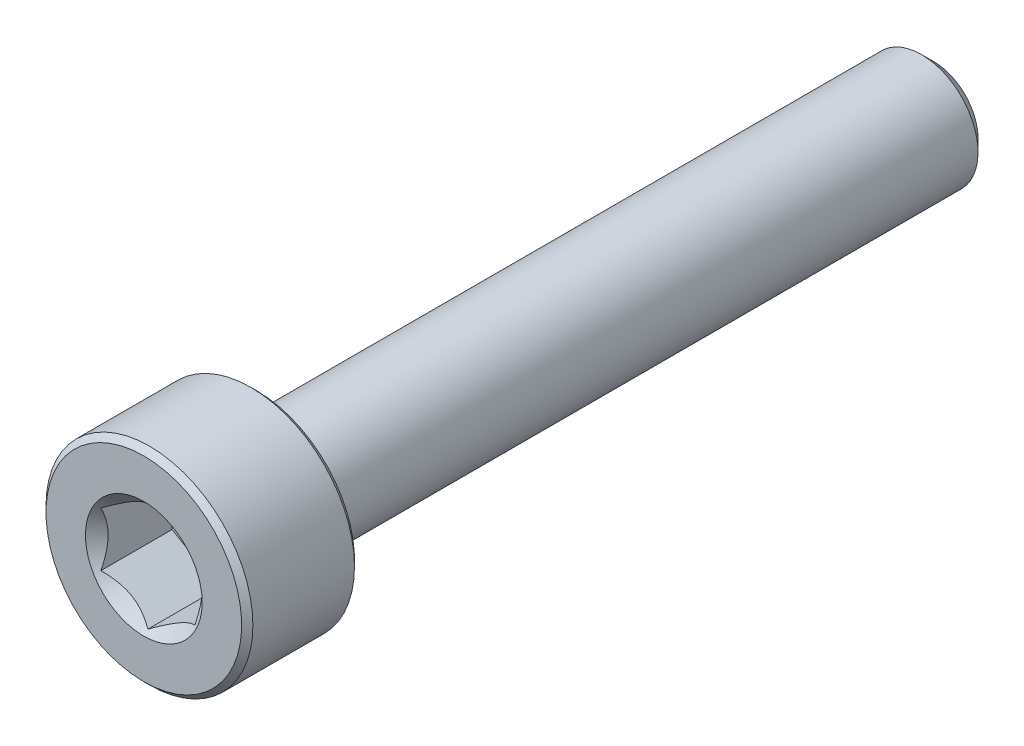
SolidWorks part; units mm, degrees
ref_plane "Front Plane" through (0, 0, 0) normal (0, 0, 1) x (1, 0, 0)
ref_plane "Top Plane" through (0, 0, 0) normal (0, 1, 0) x (1, 0, 0)
ref_plane "Right Plane" through (0, 0, 0) normal (1, 0, 0) x (0, 0, -1)
sketch "Sketch1" plane through (0, 0, 0) normal (1, 0, 0) x (0, 0, -1)
  line L0 (-10.5, 0) -> (10.5, 0) construction
  line L1 (10.5, 0) -> (10.5, 1.1752) construction
  line L2 (10.5, 1.1752) -> (10.1752, 1.5) construction
  line L3 (10.1752, 1.5) -> (10.125, 1.5) construction
  line L4 (10.125, 1.5) -> (-7.5, 1.5) construction
  line L5 (-7.5, 1.5) -> (-7.5, 2.75) construction
  line L6 (-7.5, 2.75) -> (-10.5, 2.75) construction
  line L7 (-10.5, 2.75) -> (-10.5, 0) construction
  line L8 (10.5, 1.1752) -> (10.5, 1.5) construction
  line L9 (10.4688, 1.5541) -> (10.7188, 1.1211) construction
  line L10 (10.7188, 1.1211) -> (10.9688, 1.5541) construction
  line L11 (10.9688, 1.5541) -> (10.4688, 1.5541) construction
  line L12 (10.7188, 1.5541) -> (10.7188, 1.5) construction
  line L13 (10.7188, 1.1211) -> (10.7188, 1.1752) construction
  line L14 (10.6875, 1.1752) -> (10.75, 1.1752) construction
  line L15 (10.5, 1.5) -> (10.9375, 1.5) construction
  line L16 (10.4844, 1.5271) -> (10.9531, 1.5271) construction
  line L17 (10.5, 0) -> (10.5, -1.5) construction
  line L18 (-7.65, 2.75) -> (-7.5, 2.6) construction
  line L19 (-10.35, 2.75) -> (-10.5, 2.6) construction
  line L20 (-7.5, 1.5) -> (-7.5, 0) construction
  line L21 (-7.5, 0.75) -> (-1.5, 0.75) construction
  line L22 (-1.5, 0.75) -> (4.5, 0.75) construction
  line L23 (4.5, 0.75) -> (10.5, 0.75) construction
  line L24 (-1.5, 0.75) -> (-1.5, 1.5) construction
  line L25 (-1.5, 1.5) -> (-1.5, 2.75) construction
  line L26 (4.5, 0.75) -> (4.5, 2.75) construction
  point P0 (-10.5, 1.25)
  point P3 (9.25, 1.5)
  point P4 (0, 0)
  point P18 (4.5, 1.5)
  point P22 (10.7188, 1.1752)
  point P24 (10.125, 1.5)
  point P25 (10.7188, 1.5)
  point P28 (10.7188, 1.5271)
  point P29 (9.25, -1.5)
  point P30 (-1.5, 1.5)
  point P31 (-9, 2.75)
  point P37 (-8.025, 2.75)
  point P38 (-10.275, 2.75)
  point P45 (-1.5, 0.75)
  point P46 (4.5, 0.75)
  dimension "D2" = 0.0625
  dimension "D7" = 0.15
  dimension "D8" = 0.15
  dimension "D9" = 0.15
  dimension "D10" = 0.075
  dimension "D11" = 0.375
  dimension "Drive Size" = 2.5
  dimension "Head Diameter" = 5.5
  dimension "Head Height" = 3
  dimension "Thread Pitch" = 0.5
  dimension "Thread Dia" = 3
  dimension "Length" = 18
  dimension "D12" = 0.375
  dimension "D4" = 1.25
  dimension "D3" = 45
sketch "Sketch2" plane through (0, 0, 0) normal (1, 0, 0) x (0, 0, -1)
  line L0 (-10.5, 0) -> (-10.5, 2.6)
  line L1 (-10.35, 2.75) -> (-7.65, 2.75)
  line L2 (-7.5, 2.6) -> (-7.5, 1.65)
  line L4 (10.1752, 1.5) -> (10.5, 1.1752)
  line L5 (10.5, 1.1752) -> (10.5, 0)
  line L6 (-7.5, 2.75) -> (-10.5, 2.75) construction
  line L7 (10.5, 0) -> (-10.5, 0)
  line L8 (-10.35, 2.75) -> (-10.5, 2.6) construction
  line L10 (-10.35, 2.75) -> (-10.5, 2.6)
  line L14 (-7.65, 2.75) -> (-7.5, 2.6) construction
  line L16 (-7.65, 2.75) -> (-7.5, 2.6)
  line L17 (-7.5, 1.5) -> (-7.5, 2.75) construction
  line L19 (-7.35, 1.5) -> (10.1752, 1.5)
  line L20 (10.125, 1.5) -> (-7.5, 1.5) construction
  arc A1 (-7.5, 1.65) -> (-7.35, 1.5) centre (-7.35, 1.65) ccw
  dimension "D3" = 0.15
revolve "Revolve1" add sketch "Sketch2" angle 360 about L7
sketch "Sketch3" plane through (0, 0, 10.5) normal (0, 0, 1) x (1, 0, 0)
  line L1 (1.25, -0.7217) -> (1.25, 0.7217)
  line L2 (1.25, 0.7217) -> (0, 1.4434)
  line L3 (0, 1.4434) -> (-1.25, 0.7217)
  line L4 (-1.25, 0.7217) -> (-1.25, -0.7217)
  line L5 (-1.25, -0.7217) -> (0, -1.4434)
  line L6 (0, -1.4434) -> (1.25, -0.7217)
  circle A0 centre (0, 0) radius 1.25 construction
  circle A1 centre (0, 0) radius 2.75 construction
  circle A2 centre (0, 0) radius 2.75 construction
  circle A3 centre (0, 0) radius 1.4434 construction
  point P13 (0, 0)
  dimension "D1" = 2.8868
extrude "Cut-Extrude1" cut sketch "Sketch3" against normal offset from surface (2 mm away) 1 up to face at (0, 2.6, 7.5)
sketch "Sketch4" plane through (0, 0, 10.5) normal (0, 0, 1) x (1, 0, 0)
  circle A0 centre (0, 0) radius 1.5516
  dimension "D1" = 3.1033
extrude "Cut-Extrude2" cut sketch "Sketch4" against normal up to vertex (1.5 mm away) draft 45 up to point (0, 2.75, 9)
sketch "Sketch11" plane through (0, 0, 0) normal (1, 0, 0) x (0, 0, -1)
  line L0 (-10.5, 0) -> (10.5, 0) construction
  line L1 (-10.5, 0) -> (10.5, 0) construction
  line L2 (-4.125, 0) -> (-4.125, 1.5) construction
  line L3 (10.125, 1.5) -> (-7.5, 1.5) construction
  line L4 (7.125, 0) -> (7.125, 1.5) construction
  line L6 (10.5, 1.1752) -> (10.5, 1.5) construction
  point P2 (-4.125, 0)
  point P3 (7.125, 0)
  dimension "D1" = 3.375
  dimension "D2" = 3.375
sketch "Sketch6" [suppressed] plane through (0, 0, -10.5) normal (0, 0, -1) x (-1, 0, 0)
  circle A0 centre (0, 0) radius 1.5
curve "Helix/Spiral1" [suppressed] pitch 0.5 height 18.5 turns 37
sketch "Sketch10" [suppressed] plane through (0, 0, 0) normal (1, 0, 0) x (0, 0, -1)
  line L0 (-7.35, -2.75) -> (-7.35, 2.75)
  line L5 (-10.5, 0) -> (10.5, 0) construction
  line L6 (-7.35, 1.5) -> (-7.35, -1.5) construction
  point P3 (-7.35, 0)
split "Split1" [suppressed] bodies to split 106
sketch "Sketch7" [suppressed] plane through (0, 0, 0) normal (1, 0, 0) x (0, 0, -1)
  line L0 (10.4844, 1.5271) -> (10.9531, 1.5271)
  line L1 (10.9531, 1.5271) -> (10.75, 1.1752)
  line L2 (10.75, 1.1752) -> (10.6875, 1.1752)
  line L3 (10.6875, 1.1752) -> (10.4844, 1.5271)
sweep "Cut-Sweep1" [suppressed] cut profiles "Sketch7" path "Helix/Spiral1"
sketch "Sketch8" [suppressed] plane through (0, 0, 0) normal (1, 0, 0) x (0, 0, -1)
  line L0 (-7.5, 0) -> (-7.5, 1.5)
  line L1 (-7.35, -1.5) -> (-7.35, 1.5) construction
  line L2 (-7.5, 1.5) -> (-7.35, 1.5)
  line L4 (-7.35, 1.5) -> (-6.484, 0)
  line L5 (-6.484, 0) -> (-7.5, 0)
  line L6 (10.125, 1.5) -> (-7.5, 1.5) construction
  line L7 (-10.5, 0) -> (10.5, 0) construction
  dimension "D1" = 60
revolve "Revolve2" [suppressed] add sketch "Sketch8" angle 360 about L5
equation "\"D2@Sketch1\" = \"Thread Pitch@Sketch1\" / 8"
equation "\"D4@Helix/Spiral1\" = \"Thread Pitch@Sketch1\""
equation "\"D7@Sketch1\" = \"Head Height@Sketch1\" * .05"
equation "\"D8@Sketch1\"=\"D7@Sketch1\""
equation "\"D9@Sketch1\"=\"D7@Sketch1\""
equation "\"D10@Sketch1\"=\"D7@Sketch1\"/2"
equation "\"D11@Sketch1\"=\"D10@Sketch1\"*5"
equation "\"D4@Sketch1\"=\"Thread Pitch@Sketch1\"*2.5"
equation "\"D12@Sketch1\"=\"Thread Pitch@Sketch1\"*.75"
equation "\"D3@Helix/Spiral1\"=\"Length@Sketch1\"+\"Thread Pitch@Sketch1\""
equation "\"D3@Sketch2\"=\"Thread Dia@Sketch1\"*0.05"
equation "\"D1@Sketch11\"=\"Length@Sketch1\"*0.1875"
equation "\"D2@Sketch11\"=\"D1@Sketch11\""
equation "\"D1@Sketch4\"=\"D1@Sketch3\"*1.075"
